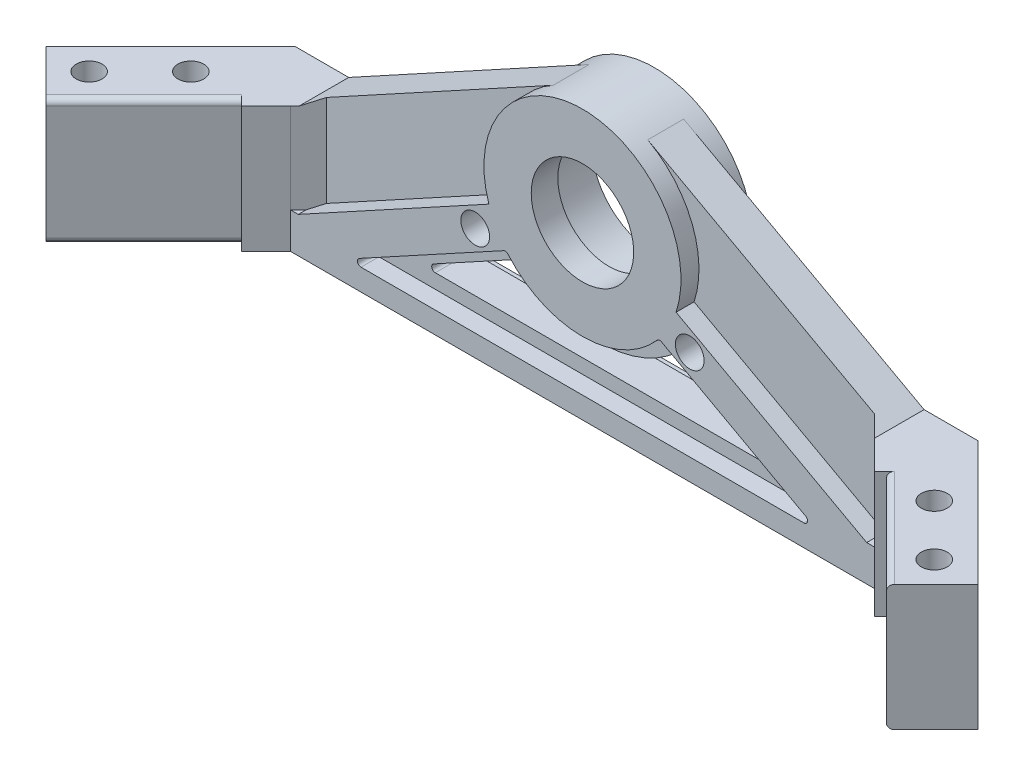
SolidWorks part; units mm, degrees
ref_plane "Front Plane" through (0, 0, 0) normal (0, 0, 1) x (1, 0, 0)
ref_plane "Top Plane" through (0, 0, 0) normal (0, 1, 0) x (1, 0, 0)
ref_plane "Right Plane" through (0, 0, 0) normal (1, 0, 0) x (0, 0, -1)
sketch "Sketch1" plane through (0, 0, 0) normal (0, 1, 0) x (-1, 0, 0)
  line L48 (74.9309, 32.5085) -> (74.2125, 33.2269)
  line L49 (74.2125, 33.2269) -> (56.9345, 15.9489)
  line L50 (57.6529, 15.2305) -> (56.9345, 15.9489)
  line L51 (-56.9345, 15.9489) -> (-74.2125, 33.2269)
  line L52 (-74.2125, 33.2269) -> (-74.9309, 32.5085)
  line L53 (-56.9345, 15.9489) -> (-57.6529, 15.2305)
  line L54 (-65.0167, 7.8667) -> (-61.5144, 4.3644)
  line L55 (-61.5144, 4.3644) -> (-52.3715, 13.5073)
  line L56 (-52.3715, 13.5073) -> (-55.8738, 17.0096)
  line L57 (-55.8738, 17.0096) -> (-65.0167, 7.8667)
  line L58 (55.8738, 17.0096) -> (52.3715, 13.5073)
  line L59 (52.3715, 13.5073) -> (61.5144, 4.3644)
  line L60 (61.5144, 4.3644) -> (65.0167, 7.8667)
  line L61 (65.0167, 7.8667) -> (55.8738, 17.0096)
  line L62 (17.3112, 9.525) -> (13.6482, 9.525)
  line L63 (17.3112, 12.7) -> (-17.3112, 12.7)
  line L64 (-13.6482, 9.525) -> (-17.3112, 9.525)
  line L65 (-17.3112, 3.175) -> (-13.6482, 3.175)
  line L66 (-17.3112, 0) -> (17.3112, 0)
  line L67 (13.6482, 3.175) -> (17.3112, 3.175)
  line L68 (-17.3112, 12.7) -> (-53.1788, 12.7)
  line L69 (-53.1788, 12.7) -> (-50.0038, 9.525)
  line L70 (-50.0038, 9.525) -> (-17.3112, 9.525)
  line L71 (-60.325, 3.175) -> (-57.15, 0)
  line L72 (-57.15, 0) -> (-17.3112, 0)
  line L73 (-17.3112, 3.175) -> (-60.325, 3.175)
  line L74 (17.3112, 9.525) -> (50.0038, 9.525)
  line L75 (50.0038, 9.525) -> (53.1788, 12.7)
  line L76 (53.1788, 12.7) -> (17.3112, 12.7)
  line L77 (57.15, 0) -> (60.325, 3.175)
  line L78 (60.325, 3.175) -> (17.3112, 3.175)
  line L79 (17.3112, 0) -> (57.15, 0)
  line L80 (-74.9309, 32.5085) -> (-82.2947, 25.1447)
  line L81 (-82.2947, 25.1447) -> (-65.0167, 7.8667)
  line L82 (-65.0167, 7.8667) -> (-57.6529, 15.2305)
  line L83 (-60.325, 3.175) -> (-13.6482, 3.175)
  line L84 (-13.6482, 9.525) -> (-50.0038, 9.525)
  line L85 (-50.0038, 9.525) -> (-53.1788, 12.7)
  line L86 (-53.1788, 12.7) -> (-61.5144, 4.3644)
  line L87 (-61.5144, 4.3644) -> (-60.325, 3.175)
  line L88 (13.6482, 3.175) -> (60.325, 3.175)
  line L89 (60.325, 3.175) -> (61.5144, 4.3644)
  line L90 (61.5144, 4.3644) -> (53.1788, 12.7)
  line L91 (53.1788, 12.7) -> (50.0038, 9.525)
  line L92 (50.0038, 9.525) -> (13.6482, 9.525)
  line L93 (82.2947, 25.1447) -> (74.9309, 32.5085)
  line L94 (57.6529, 15.2305) -> (65.0167, 7.8667)
  line L95 (65.0167, 7.8667) -> (82.2947, 25.1447)
sketch "Sketch3" plane through (0, 0, 0) normal (0, 1, 0) x (1, 0, 0)
  line L0 (-53.1788, -12.7) -> (-17.3112, -12.7) construction
  line L1 (-17.3112, 0) -> (-57.15, 0) construction
  line L2 (-57.15, 0) -> (-60.325, -3.175) construction
  line L3 (-60.325, -3.175) -> (-61.5144, -4.3644) construction
  line L4 (-61.5144, -4.3644) -> (-65.0167, -7.8667) construction
  line L5 (-74.2125, -33.2269) -> (-56.9345, -15.9489) construction
  line L6 (-74.9309, -32.5085) -> (-74.2125, -33.2269) construction
  line L7 (-82.2947, -25.1447) -> (-74.9309, -32.5085) construction
  line L8 (-65.0167, -7.8667) -> (-82.2947, -25.1447) construction
  line L9 (-51.5642, -12.7) -> (-17.3112, -12.7)
  line L10 (-17.3112, 0) -> (-57.15, 0)
  line L11 (-57.15, 0) -> (-60.325, -3.175)
  line L12 (-60.325, -3.175) -> (-61.5144, -4.3644)
  line L13 (-61.5144, -4.3644) -> (-65.0167, -7.8667)
  line L14 (-74.2125, -33.2269) -> (-56.9345, -15.9489)
  line L15 (-74.9309, -32.5085) -> (-74.2125, -33.2269)
  line L16 (-82.2947, -25.1447) -> (-74.9309, -32.5085)
  line L17 (-65.0167, -7.8667) -> (-82.2947, -25.1447)
  line L18 (0, 0) -> (0, -12.7) construction
  line L19 (-17.3112, -12.7) -> (17.3112, -12.7) construction
  line L20 (17.3112, 0) -> (-17.3112, 0) construction
  line L21 (-52.3715, -13.5073) -> (-61.5144, -4.3644) construction
  line L22 (-65.0167, -7.8667) -> (-55.8738, -17.0096) construction
  line L23 (-55.8738, -17.0096) -> (-52.3715, -13.5073) construction
  line L24 (17.3112, 0) -> (-17.3112, 0)
  line L25 (-17.3112, -12.7) -> (17.3112, -12.7)
  line L26 (-52.3715, -13.5073) -> (-61.5144, -4.3644)
  line L27 (-65.0167, -7.8667) -> (-55.8738, -17.0096)
  line L28 (-55.8738, -17.0096) -> (-52.3715, -13.5073)
  line L29 (55.8738, -17.0096) -> (52.3715, -13.5073)
  line L30 (65.0167, -7.8667) -> (55.8738, -17.0096)
  line L31 (52.3715, -13.5073) -> (61.5144, -4.3644)
  line L32 (65.0167, -7.8667) -> (82.2947, -25.1447)
  line L33 (82.2947, -25.1447) -> (74.9309, -32.5085)
  line L34 (74.9309, -32.5085) -> (74.2125, -33.2269)
  line L35 (74.2125, -33.2269) -> (56.9345, -15.9489)
  line L36 (61.5144, -4.3644) -> (65.0167, -7.8667)
  line L37 (60.325, -3.175) -> (61.5144, -4.3644)
  line L38 (57.15, 0) -> (60.325, -3.175)
  line L39 (17.3112, 0) -> (57.15, 0)
  line L40 (51.5642, -12.7) -> (17.3112, -12.7)
  line L41 (-52.3715, -13.5073) -> (-51.5642, -12.7)
  line L42 (52.3715, -13.5073) -> (51.5642, -12.7)
extrude "Boss-Extrude1" add sketch "Sketch3" along normal mid plane 22.225 contours L27 L17 L16 L15 L14 | L27 L28 L26 L13 | L18 L24 L10 L11 L12 L26 L41 L9 L25 | L24 L18 L25 L40 L42 L31 L37 L38 L39 | L36 L31 L29 L30 | L35 L34 L33 L32 L30 region at (-29.0802, 0, 6.2508) region at (-58.6941, 0, 10.687) region at (29.0802, 0, 6.2508) region at (-69.6146, 0, 20.5468) region at (58.6941, 0, 10.687) region at (69.6146, 0, 20.5468)
sketch "Sketch2" plane through (0, 0, 0) normal (0, 0, 1) x (1, 0, 0)
  line L0 (0, 0) -> (0, 36.45) construction
  line L1 (-17.3112, 0) -> (17.3112, 0) construction
  line L2 (50.8048, 11.1125) -> (8.3447, 34.3184)
  line L3 (-50.8048, 11.1125) -> (-8.3447, 34.3184)
  line L4 (50.8048, 11.1125) -> (15.4841, 11.1125)
  line L5 (57.15, 11.1125) -> (-57.15, 11.1125) construction
  line L6 (-50.8048, 11.1125) -> (-15.4841, 11.1125)
  circle A0 centre (0, 19.05) radius 11.05
  circle A1 centre (0, 19.05) radius 17.4
  circle A2 centre (0, 19.05) radius 9.05
  dimension "D1" = 22.1
  dimension "D2" = 6.35
  dimension "D4" = 2
  dimension "D3" = 19.05
extrude "Boss-Extrude2" add sketch "Sketch2" along normal up to surface (12.7 mm away) contours A1 L3 L6 | A1 L0 A0 | A0 L0 | L0 A0 | L0 A1 A0 | A1 L4 L2 | A2 region at (-8.8704, 4.5349, 0) region at (0.3891, 4.825, 0) region at (-10.8029, 19.05, 0) region at (0.2471, 9, 0) region at (-27.6614, 17.7256, 0) region at (27.6614, 17.7256, 0) up to face at (0, 0, 12.7)
extrude "Cut-Extrude2" cut sketch "Sketch2<3>" along normal blind 8 contours A0 L0 A2 | A2 L0 | L0 A2 | L0 A0 A2 region at (-10.8029, 19.05, 0) region at (0.2471, 9, 0) region at (-3.8409, 19.05, 0) region at (3.8409, 19.05, 0)
sketch "Sketch2<3>" plane through (0, 0, 0) normal (0, 0, 1) x (1, 0, 0) same geometry as "Sketch2"
extrude "Cut-Extrude3" cut sketch "Sketch2<5>" along normal through all contours A2 L0 | L0 A2 region at (-3.8409, 19.05, 0) region at (3.8409, 19.05, 0)
sketch "Sketch2<5>" plane through (0, 0, 0) normal (0, 0, 1) x (1, 0, 0) same geometry as "Sketch2"
sketch "Sketch5" plane through (0, 0, 0) normal (0, 0, -1) x (-1, 0, 0)
  line L0 (-16.5348, 13.6314) -> (-57.15, -8.5663)
  line L1 (-48.5682, -11.1125) -> (-13.4894, 8.0593)
  line L2 (0, 19.05) -> (-55.1885, -11.1125) construction
  line L3 (0, 19.05) -> (0, -11.1125) construction
  line L4 (16.5348, 13.6314) -> (57.15, -8.5663)
  line L5 (48.5682, -11.1125) -> (13.4894, 8.0593)
  line L6 (0, 19.05) -> (55.1885, -11.1125) construction
  line L7 (57.15, 11.1125) -> (50.8048, 11.1125)
  line L8 (50.8048, 11.1125) -> (8.3447, 34.3184)
  line L9 (-8.3447, 34.3184) -> (-50.8048, 11.1125)
  line L10 (-50.8048, 11.1125) -> (-57.15, 11.1125)
  line L11 (-57.15, 11.1125) -> (-57.15, -11.1125)
  line L12 (-57.15, -11.1125) -> (57.15, -11.1125)
  line L13 (57.15, -11.1125) -> (57.15, 11.1125)
  line L14 (57.15, 11.1125) -> (50.8048, 11.1125)
  line L15 (50.8048, 11.1125) -> (8.3447, 34.3184)
  line L16 (-8.3447, 34.3184) -> (-50.8048, 11.1125)
  line L17 (-50.8048, 11.1125) -> (-57.15, 11.1125)
  line L18 (-57.15, 11.1125) -> (-57.15, -11.1125)
  line L19 (-57.15, -11.1125) -> (57.15, -11.1125)
  line L20 (57.15, -11.1125) -> (57.15, 11.1125)
  line L21 (-41.597, -7.3025) -> (41.597, -7.3025)
  line L22 (-31.6533, -4.7625) -> (31.6533, -4.7625)
  line L23 (-31.6533, -4.7625) -> (-14.0224, 4.8734)
  line L24 (31.6533, -4.7625) -> (14.0224, 4.8734)
  line L25 (-57.15, 11.1125) -> (-82.2947, 11.1125)
  line L26 (-82.2947, 11.1125) -> (-82.2947, -11.1125)
  line L27 (-82.2947, -11.1125) -> (-57.15, -11.1125)
  line L28 (-82.2947, -4.7625) -> (-50.1902, -4.7625)
  line L29 (82.2947, -4.7625) -> (50.1902, -4.7625)
  line L33 (57.15, -11.1125) -> (82.2947, -11.1125)
  line L34 (82.2947, -11.1125) -> (82.2947, 11.1125)
  line L35 (82.2947, 11.1125) -> (57.15, 11.1125)
  line L36 (57.15, 11.1125) -> (57.15, -11.1125)
  line L37 (57.15, -11.1125) -> (82.2947, -11.1125)
  line L38 (82.2947, -11.1125) -> (82.2947, 11.1125)
  line L39 (82.2947, 11.1125) -> (57.15, 11.1125)
  line L40 (57.15, 11.1125) -> (57.15, -11.1125)
  circle A0 centre (0, 19.05) radius 11.05 construction
  arc A1 (8.3447, 34.3184) -> (-8.3447, 34.3184) centre (0, 19.05) ccw
  arc A2 (8.3447, 34.3184) -> (-8.3447, 34.3184) centre (0, 19.05) ccw
  circle A3 centre (0, 19.05) radius 11.05
  circle A4 centre (0, 19.05) radius 17.4
  arc A5 (-14.0224, 4.8734) -> (14.0224, 4.8734) centre (0, 19.05) ccw
  circle A6 centre (0, 19.05) radius 19.94 construction
  line M30 (57.15, 11.1125) -> (50.8048, 11.1125)
  line M31 (50.8048, 11.1125) -> (8.3447, 34.3184)
  line M33 (-8.3447, 34.3184) -> (-50.8048, 11.1125)
  line M34 (-50.8048, 11.1125) -> (-57.15, 11.1125)
  line M35 (-57.15, 11.1125) -> (-57.15, -11.1125)
  dimension "D2" = 3.175
  dimension "D3" = 3.175
  dimension "D4" = 3.81
  dimension "D6" = 2.54
  dimension "D7" = 2.54
  dimension "D9" = 6.35
  dimension "D1" = 0
  dimension "D5" = 2.54
  dimension "D8" = 0
extrude "Cut-Extrude4" cut sketch "Sketch5" against normal blind 3.175 contours L26 L28 L25 M35 | A4 L28 L0 M33 M34 M35 | A4 L4 L29 L20 M30 M31 | L38 L39 L20 L29 | A4 L1 L21 L5 L23 A5 L24 L22 region at (36.5899, 11.2064, 0) region at (0, 0.804, 0) region at (69.7224, 3.175, 0) region at (-36.5899, 11.2064, 0) region at (-69.7224, 3.175, 0)
extrude "Cut-Extrude5" cut sketch "Sketch5<3>" against normal through all contours A5 L23 L22 L24 region at (0, -1.6144, 0)
sketch "Sketch5<3>" plane through (0, 0, 0) normal (0, 0, -1) x (-1, 0, 0) same geometry as "Sketch5"
sketch "Sketch6" plane through (0, 0, 0) normal (0, 0, -1) x (-1, 0, 0)
  line L0 (0, 19.05) -> (-18.9451, 8.6958) construction
  line L1 (-16.5348, 13.6314) -> (-50.1902, -4.7625) construction
  line L2 (0, 19.05) -> (0, 0) construction
  circle A0 centre (0, 19.05) radius 11.05 construction
  circle A1 centre (0, 19.05) radius 11.05 construction
  circle A2 centre (-18.9451, 8.6958) radius 2.54
  circle A3 centre (18.9451, 8.6958) radius 2.54
  dimension "D2" = 5.08
  dimension "D1" = 21.59
extrude "Cut-Extrude6" cut sketch "Sketch6" against normal through all contours A2 | A3 region at (18.9451, 8.6958, 0) region at (-18.9451, 8.6958, 0)
sketch "Sketch7" plane through (0, 0, 12.7) normal (0, 0, 1) x (1, 0, 0)
  line L0 (0, 19.05) -> (-51.5642, -9.1317) construction
  line L1 (0, 19.05) -> (0, 0) construction
  line L2 (0, 19.05) -> (51.5642, -9.1317) construction
  line L3 (-51.5642, -5.5134) -> (-8.9593, 17.7717)
  line L4 (-50.1902, -4.7625) -> (-51.5642, -4.7625)
  line L5 (-48.5189, -11.0856) -> (-5.9139, 12.1996)
  line L6 (48.5189, -11.0856) -> (5.9139, 12.1996)
  line L7 (51.5642, 11.1125) -> (50.8048, 11.1125)
  line L8 (50.8048, 11.1125) -> (8.3447, 34.3184)
  line L9 (-8.3447, 34.3184) -> (-50.8048, 11.1125)
  line L10 (-50.8048, 11.1125) -> (-51.5642, 11.1125)
  line L11 (-51.5642, 11.1125) -> (-51.5642, -11.1125)
  line L12 (-51.5642, -11.1125) -> (51.5642, -11.1125)
  line L13 (51.5642, -11.1125) -> (51.5642, 11.1125)
  line L14 (51.5642, 11.1125) -> (50.8048, 11.1125)
  line L15 (50.8048, 11.1125) -> (8.3447, 34.3184)
  line L16 (-8.3447, 34.3184) -> (-50.8048, 11.1125)
  line L17 (-50.8048, 11.1125) -> (-51.5642, 11.1125)
  line L18 (-51.5642, 11.1125) -> (-51.5642, -11.1125)
  line L19 (-51.5642, -11.1125) -> (51.5642, -11.1125)
  line L20 (51.5642, -11.1125) -> (51.5642, 11.1125)
  line L21 (50.1902, -4.7625) -> (51.5642, -4.7625)
  line L22 (51.5642, -5.5134) -> (8.9593, 17.7717)
  line L23 (-41.597, -7.3025) -> (41.597, -7.3025)
  circle A0 centre (0, 19.05) radius 9.05 construction
  arc A1 (8.3447, 34.3184) -> (-8.3447, 34.3184) centre (0, 19.05) ccw
  arc A2 (8.3447, 34.3184) -> (-8.3447, 34.3184) centre (0, 19.05) ccw
  circle A3 centre (0, 19.05) radius 9.05
  circle A4 centre (0, 19.05) radius 9.05
  circle A8 centre (0, 19.05) radius 17.4
  arc M19 (-14.0224, 4.8734) -> (14.0224, 4.8734) centre (0, 19.05) ccw
  line M21 (14.0224, 4.8734) -> (31.6533, -4.7625)
  line M23 (31.6533, -4.7625) -> (-31.6533, -4.7625)
  line M25 (-31.6533, -4.7625) -> (-14.0224, 4.8734)
  line M28 (51.5642, 11.1125) -> (50.8048, 11.1125)
  line M29 (50.8048, 11.1125) -> (8.3447, 34.3184)
  line M31 (-8.3447, 34.3184) -> (-50.8048, 11.1125)
  line M32 (-50.8048, 11.1125) -> (-51.5642, 11.1125)
  line M33 (-51.5642, 11.1125) -> (-51.5642, -11.1125)
  dimension "D2" = 6.35
  dimension "D3" = 6.35
  dimension "D4" = 3.81
  dimension "D1" = 0
extrude "Cut-Extrude7" cut sketch "Sketch7" against normal blind 3.175 contours A8 L5 L23 L6 M19 M21 M23 M25 | A8 L4 L3 M31 M32 M33 | A8 L22 L21 L20 M28 M29 region at (-33.839, 12.4499, 12.7) region at (0, 0.804, 12.7) region at (33.839, 12.4499, 12.7)
chamfer "Chamfer1" distance 3.175 angle 45 2 edges at (51.5642, 3.175, 9.525) (-51.5642, 3.175, 9.525)
fillet "Fillet1" radius 0.635 12 edges at (-41.597, -7.3025, 1.5875) (41.597, -7.3025, 1.5875) (13.4894, 8.0593, 1.5875) (-13.4894, 8.0593, 1.5875) (14.0224, 4.8734, 6.35) (-14.0224, 4.8734, 6.35) (-31.6533, -4.7625, 6.35) (31.6533, -4.7625, 6.35) (41.597, -7.3025, 11.1125) (-41.597, -7.3025, 11.1125) (13.4894, 8.0593, 11.1125) (-13.4894, 8.0593, 11.1125)
fillet "Fillet3" radius 1.016 4 edges at (-65.5735, -11.1125, 24.5879) (65.5735, -11.1125, 24.5879) (-65.5735, 11.1125, 24.5879) (65.5735, 11.1125, 24.5879)
sketch "Sketch8" plane through (0, 11.1125, 0) normal (0, 1, 0) x (1, 0, 0)
  line L0 (57.6529, -15.2305) -> (55.8738, -17.0096) construction
  line L1 (57.6529, -15.2305) -> (55.8738, -17.0096)
  line L2 (0, 0) -> (0, -12.7) construction
  line L3 (17.4, 0) -> (-17.4, 0) construction
  line L4 (-17.4, -12.7) -> (17.4, -12.7) construction
  line L5 (57.6529, -15.2305) -> (65.0167, -7.8667)
  line L6 (60.325, -3.175) -> (82.2947, -25.1447) construction
  line L7 (61.1552, -11.7282) -> (78.4332, -29.0062) construction
  line L8 (82.2947, -25.1447) -> (74.9309, -32.5085) construction
  line L10 (-57.6529, -15.2305) -> (-55.8738, -17.0096)
  line L11 (-57.6529, -15.2305) -> (-65.0167, -7.8667)
  line L12 (-61.1552, -11.7282) -> (-78.4332, -29.0062) construction
  circle A0 centre (65.6453, -16.2183) radius 2.286
  circle A1 centre (74.6256, -25.1986) radius 2.286
  circle A2 centre (-65.6453, -16.2183) radius 2.286
  circle A3 centre (-74.6256, -25.1986) radius 2.286
  dimension "D2" = 4.572
  dimension "D3" = 4.572
  dimension "D1" = 5.461
  dimension "D4" = 6.35
  dimension "D5" = 12.7
extrude "Cut-Extrude8" cut sketch "Sketch8" against normal through all contours A1 | A3 | A0 | A2 region at (74.6256, 11.1125, 25.1986) region at (-74.6256, 11.1125, 25.1986)
